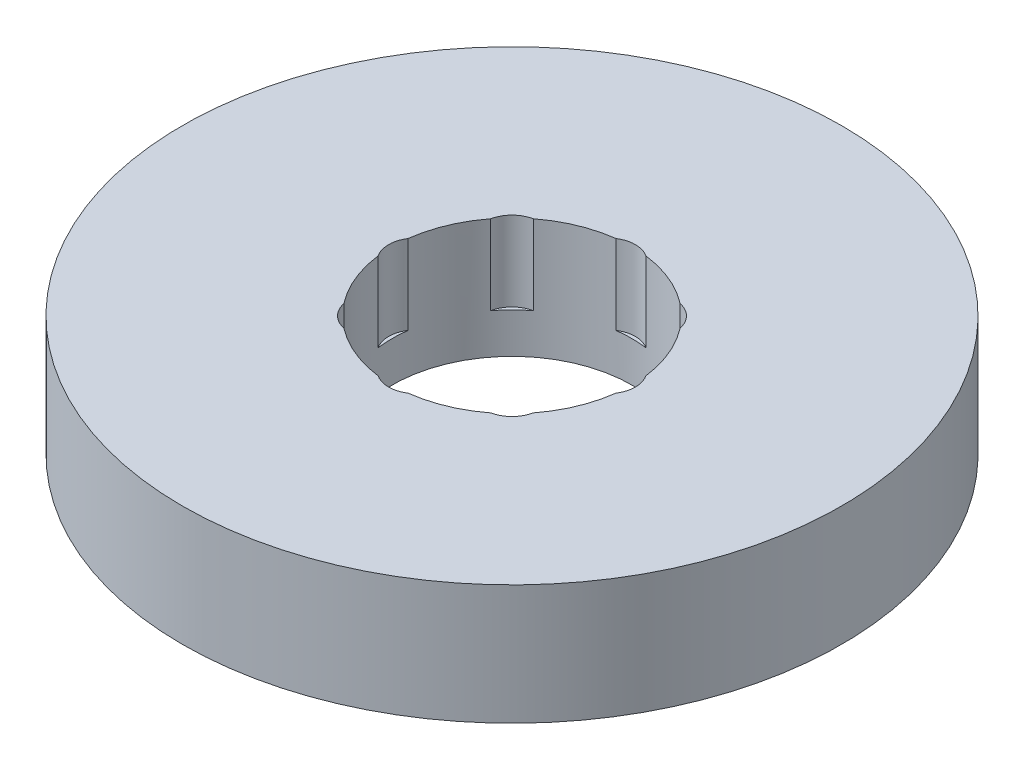
SolidWorks part; units mm, degrees
ref_plane "Front Plane" through (0, 0, 0) normal (0, 0, 1) x (1, 0, 0)
ref_plane "Top Plane" through (0, 0, 0) normal (0, 1, 0) x (1, 0, 0)
ref_plane "Right Plane" through (0, 0, 0) normal (1, 0, 0) x (0, 0, -1)
sketch "Sketch1" plane through (0, 0, 0) normal (0, 1, 0) x (1, 0, 0)
  circle A0 centre (0, 0) radius 82.5
  dimension "FLANGE_OD" = 165
extrude "Boss-Extrude1" add sketch "Sketch1" along normal blind 30
sketch "Sketch2" plane through (0, 0, 0) normal (0, 1, 0) x (1, 0, 0)
  circle A0 centre (0, 0) radius 30
  dimension "BORE_D" = 60
extrude "Cut-Extrude1" cut sketch "Sketch2" along normal through all
sketch "Sketch3" plane through (0, 30, 0) normal (0, 1, 0) x (1, 0, 0)
  circle A0 centre (0, 0) radius 23.9977 construction
  circle A1 centre (-23.9977, 0) radius 6.886
  dimension "BOLT_D" = 13.7721
  dimension "BOLT_PCD" = 47.9953
extrude "Cut-Extrude2" cut sketch "Sketch3" against normal blind 19.9159
pattern_circular "CirPattern1" count 8 over 360 about axis through (0, 0, 0) along (0, 1, 0) of "Cut-Extrude2"
